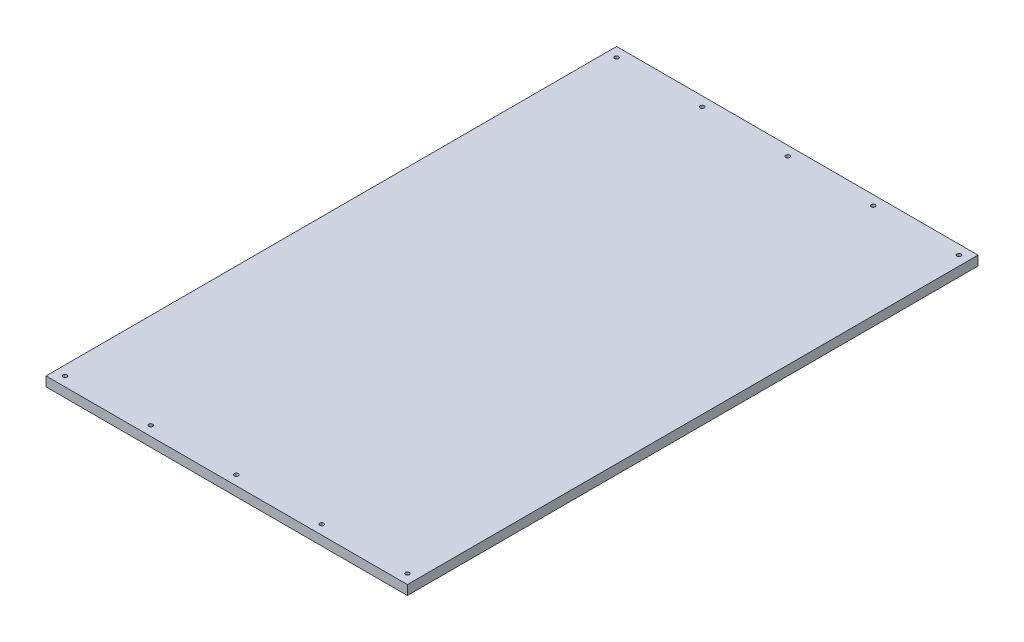
SolidWorks part; units mm, degrees
ref_plane "Front Plane" through (0, 0, 0) normal (0, 0, 1) x (1, 0, 0)
ref_plane "Top Plane" through (0, 0, 0) normal (0, 1, 0) x (1, 0, 0)
ref_plane "Right Plane" through (0, 0, 0) normal (1, 0, 0) x (0, 0, -1)
sketch "Sketch1" plane through (0, 0, 0) normal (0, 1, 0) x (1, 0, 0)
  line L1 (-190, 300) -> (190, 300)
  line L2 (-190, 300) -> (-190, -300)
  line L3 (-190, -300) -> (190, -300)
  line L4 (190, 300) -> (190, -300)
  line L5 (-190, 300) -> (190, -300) construction
  line L6 (-190, -300) -> (190, 300) construction
  point P0 (0, 0)
  dimension "D1" = 600
  dimension "D2" = 380
extrude "Boss-Extrude1" add sketch "Sketch1" along normal blind 10
sketch "Sketch2" plane through (0, 10, 0) normal (0, 1, 0) x (1, 0, 0)
  line L0 (-190, 300) -> (-190, 290) construction
  line L1 (-190, 300) -> (-190, -300) construction
  line L2 (-190, 290) -> (190, 290) construction
  line L3 (-55, 0) -> (55, 0) construction
  circle A0 centre (0, 290) radius 2.1
  circle A1 centre (90, 290) radius 2.1
  circle A2 centre (180, 290) radius 2.1
  circle A3 centre (-90, 290) radius 2.1
  circle A4 centre (-180, 290) radius 2.1
  circle A5 centre (180, -290) radius 2.1
  circle A6 centre (90, -290) radius 2.1
  circle A7 centre (0, -290) radius 2.1
  circle A8 centre (-90, -290) radius 2.1
  circle A9 centre (-180, -290) radius 2.1
  dimension "D3" = 4.2
  dimension "D4" = 4.2
  dimension "D5" = 4.2
  dimension "D6" = 4.2
  dimension "D7" = 4.2
  dimension "D1" = 10
  dimension "D2" = 380
  dimension "D8" = 10
  dimension "D9" = 90
  dimension "D10" = 10
  dimension "D11" = 90
extrude "Cut-Extrude1" cut sketch "Sketch2" against normal blind 10
